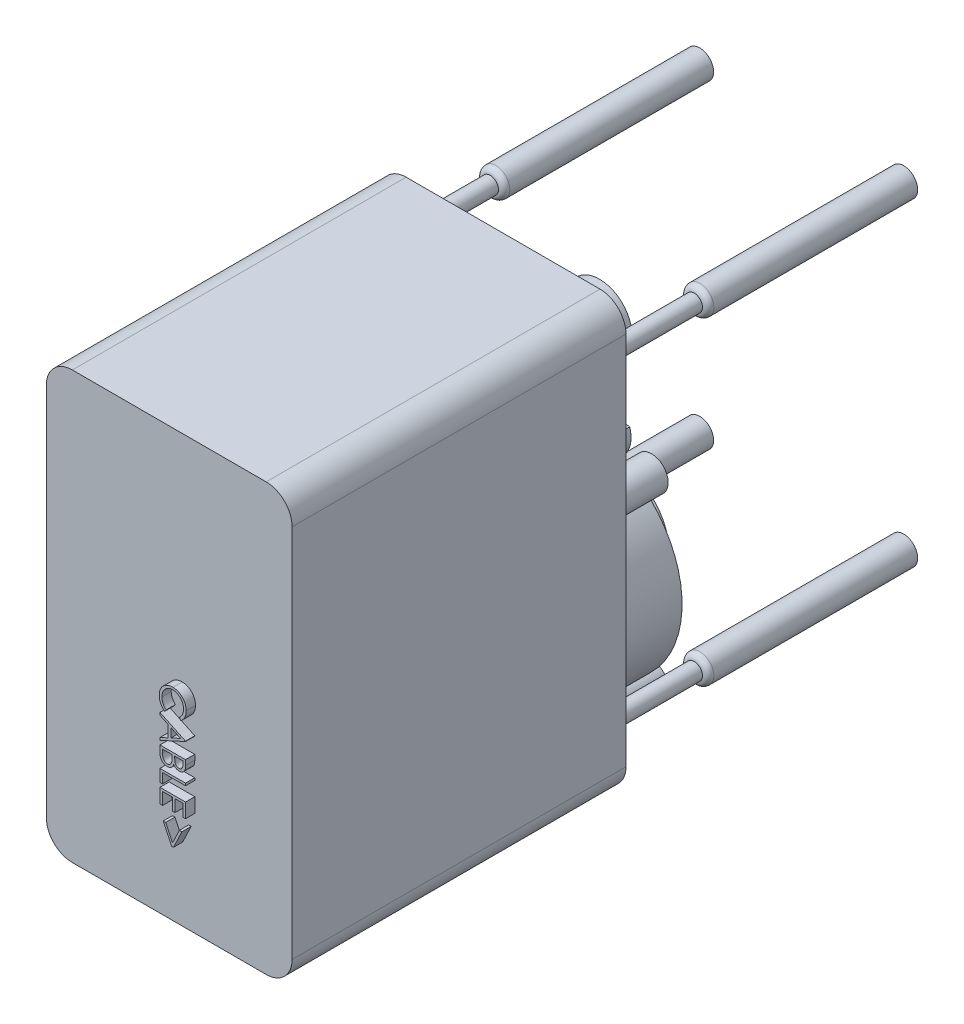
SolidWorks part; units mm, degrees
ref_plane "Front Plane" through (0, 0, 0) normal (0, 0, 1) x (1, 0, 0)
ref_plane "Top Plane" through (0, 0, 0) normal (0, 1, 0) x (1, 0, 0)
ref_plane "Right Plane" through (0, 0, 0) normal (1, 0, 0) x (0, 0, -1)
sketch "Sketch1" plane through (0, 0, 0) normal (0, 0, 1) x (1, 0, 0)
  line L0 (-13.081, 28.829) -> (13.081, 28.829)
  line L1 (-16.637, 25.273) -> (-16.637, -25.273)
  line L2 (-13.081, -28.829) -> (13.081, -28.829)
  line L3 (16.637, 25.273) -> (16.637, -25.273)
  line L4 (-16.637, 28.829) -> (16.637, -28.829) construction
  line L5 (-16.637, -28.829) -> (16.637, 28.829) construction
  line L6 (0, 36.9388) -> (0, -36.9388) construction
  line L7 (-21.0275, 0) -> (21.0275, 0) construction
  arc A0 (16.637, -25.273) -> (13.081, -28.829) centre (13.081, -25.273) cw
  arc A1 (-13.081, -28.829) -> (-16.637, -25.273) centre (-13.081, -25.273) cw
  arc A2 (16.637, 25.273) -> (13.081, 28.829) centre (13.081, 25.273) ccw
  arc A3 (-13.081, 28.829) -> (-16.637, 25.273) centre (-13.081, 25.273) ccw
  circle A4 centre (0, -12.7) radius 7.239
  circle A5 centre (0, 12.7) radius 4.445
  circle A6 centre (0, 14.605) radius 6.35
  circle A7 centre (0, -12.7) radius 14.351
  arc A8 (-3.6204, 1.1868) -> (3.6204, 1.1868) centre (0, 0) ccw
  circle A9 centre (13.97, 21.844) radius 1.016
  circle A10 centre (-13.97, 21.844) radius 1.016
  circle A11 centre (13.97, -21.844) radius 1.016
  circle A12 centre (-13.97, -21.844) radius 1.016
  arc A13 (6.6635, 0.0102) -> (10.0641, -2.4694) centre (8.89, -0.508) cw
  arc A14 (-10.0641, -2.4694) -> (-6.6635, 0.0102) centre (-8.89, -0.508) cw
  arc A15 (-10.0641, -22.9306) -> (-6.6635, -25.4102) centre (-8.89, -24.892) ccw
  arc A16 (6.6635, -25.4102) -> (10.0641, -22.9306) centre (8.89, -24.892) ccw
  point P0 (0, 0)
  dimension "D3" = 3.556
  dimension "D4" = 14.478
  dimension "D5" = 8.89
  dimension "D6" = 12.7
  dimension "D8" = 7.62
  dimension "D10" = 2.032
  dimension "D12" = 28.702
  dimension "D13" = 2.286
  dimension "D1" = 33.274
  dimension "D2" = 57.658
  dimension "D7" = 12.7
  dimension "D9" = 21.844
  dimension "D11" = 13.97
  dimension "D14" = 8.89
  dimension "D15" = 0.508
  dimension "D16" = 0.508
  dimension "D17" = 8.89
  dimension "D18" = 24.892
  dimension "D19" = 24.892
  dimension "D20" = 8.89
  dimension "D21" = 8.89
extrude "Boss-Extrude1" add sketch "Sketch1" against normal blind 10.16 contours A8 A7 A4 | A14 A7 | A7 A8 | A13 A7 | A7 A16 | A7 A15 | A4 region at (0, -12.7, 0) region at (12.8646, -18.0906, 0) region at (9.2197, -0.0559, 0) region at (9.2197, -25.3441, 0) region at (0, -0.8411, 0) region at (-9.2197, -25.3441, 0) region at (-9.2197, -0.0559, 0)
sketch "Sketch2" plane through (0, 0, 0) normal (0, 0, 1) x (1, 0, 0)
  line L0 (-13.081, 28.829) -> (13.081, 28.829)
  line L1 (-16.637, 25.273) -> (-16.637, -25.273)
  line L2 (-13.081, -28.829) -> (13.081, -28.829)
  line L3 (16.637, 25.273) -> (16.637, -25.273)
  line L4 (-16.637, 28.829) -> (16.637, -28.829) construction
  line L5 (-16.637, -28.829) -> (16.637, 28.829) construction
  line L6 (0, 38.9705) -> (0, -34.9071) construction
  line L7 (-9.8575, 0) -> (32.1974, 0) construction
  arc A0 (16.637, -25.273) -> (13.081, -28.829) centre (13.081, -25.273) cw
  arc A1 (-13.081, -28.829) -> (-16.637, -25.273) centre (-13.081, -25.273) cw
  arc A2 (16.637, 25.273) -> (13.081, 28.829) centre (13.081, 25.273) ccw
  arc A3 (-13.081, 28.829) -> (-16.637, 25.273) centre (-13.081, 25.273) ccw
  circle A4 centre (0, -12.7) radius 7.239
  circle A5 centre (0, 12.7) radius 4.445
  circle A6 centre (0, 14.605) radius 6.35
  circle A7 centre (0, -12.7) radius 14.351
  arc A8 (-3.6204, 1.1868) -> (3.6204, 1.1868) centre (0, 0) ccw
  circle A9 centre (13.97, 21.844) radius 1.016
  circle A10 centre (-13.97, 21.844) radius 1.016
  circle A11 centre (13.97, -21.844) radius 1.016
  circle A12 centre (-13.97, -21.844) radius 1.016
  arc A13 (6.6635, 0.0102) -> (10.0641, -2.4694) centre (8.89, -0.508) cw
  arc A14 (-10.0641, -2.4694) -> (-6.6635, 0.0102) centre (-8.89, -0.508) cw
  arc A15 (-10.0641, -22.9306) -> (-6.6635, -25.4102) centre (-8.89, -24.892) ccw
  arc A16 (6.6635, -25.4102) -> (10.0641, -22.9306) centre (8.89, -24.892) ccw
  point P0 (0, 0)
  dimension "D3" = 3.556
  dimension "D4" = 14.478
  dimension "D5" = 8.89
  dimension "D6" = 12.7
  dimension "D8" = 7.62
  dimension "D10" = 2.032
  dimension "D12" = 28.702
  dimension "D13" = 2.286
  dimension "D1" = 33.274
  dimension "D2" = 57.658
  dimension "D7" = 12.7
  dimension "D9" = 21.844
  dimension "D11" = 13.97
  dimension "D14" = 8.89
  dimension "D15" = 0.508
  dimension "D16" = 0.508
  dimension "D17" = 8.89
  dimension "D18" = 24.892
  dimension "D19" = 24.892
  dimension "D20" = 8.89
  dimension "D21" = 8.89
extrude "Boss-Extrude2" add sketch "Sketch2" against normal blind 1.778 separate body contours A5 | A5 A6 region at (0, 12.7, 0) region at (-4.3631, 18.9681, 0)
sketch "Sketch3" plane through (0, 0, -10.16) normal (0, 0, -1) x (-1, 0, 0)
  circle A0 centre (-8.89, -0.508) radius 2.286
  circle A1 centre (8.89, -24.892) radius 2.286
  circle A2 centre (-8.89, -24.892) radius 2.286
  circle A3 centre (8.89, -0.508) radius 2.286
extrude "Boss-Extrude3" add sketch "Sketch3" along normal blind 1.27
sketch "Sketch4" plane through (0, 0, -10.16) normal (0, 0, -1) x (-1, 0, 0)
  line L0 (-13.081, 28.829) -> (13.081, 28.829)
  line L1 (-16.637, 25.273) -> (-16.637, -25.273)
  line L2 (-13.081, -28.829) -> (13.081, -28.829)
  line L3 (16.637, 25.273) -> (16.637, -25.273)
  line L4 (-16.637, 28.829) -> (16.637, -28.829) construction
  line L5 (-16.637, -28.829) -> (16.637, 28.829) construction
  line L6 (0, 23.9866) -> (0, -49.891) construction
  line L7 (7.1619, 0) -> (49.2169, 0) construction
  arc A0 (16.637, -25.273) -> (13.081, -28.829) centre (13.081, -25.273) cw
  arc A1 (-13.081, -28.829) -> (-16.637, -25.273) centre (-13.081, -25.273) cw
  arc A2 (16.637, 25.273) -> (13.081, 28.829) centre (13.081, 25.273) ccw
  arc A3 (-13.081, 28.829) -> (-16.637, 25.273) centre (-13.081, 25.273) ccw
  circle A4 centre (0, -12.7) radius 7.239
  circle A5 centre (0, 12.7) radius 4.445
  circle A6 centre (0, 14.605) radius 6.35
  circle A7 centre (0, -12.7) radius 14.351
  arc A8 (-3.6204, 1.1868) -> (3.6204, 1.1868) centre (0, 0) ccw
  circle A9 centre (13.97, 21.844) radius 1.016
  circle A10 centre (-13.97, 21.844) radius 1.016
  circle A11 centre (13.97, -21.844) radius 1.016
  circle A12 centre (-13.97, -21.844) radius 1.016
  arc A13 (6.6635, 0.0102) -> (10.0641, -2.4694) centre (8.89, -0.508) cw
  arc A14 (-10.0641, -2.4694) -> (-6.6635, 0.0102) centre (-8.89, -0.508) cw
  arc A15 (-10.0641, -22.9306) -> (-6.6635, -25.4102) centre (-8.89, -24.892) ccw
  arc A16 (6.6635, -25.4102) -> (10.0641, -22.9306) centre (8.89, -24.892) ccw
  point P0 (0, 0)
  dimension "D3" = 3.556
  dimension "D4" = 14.478
  dimension "D5" = 8.89
  dimension "D6" = 12.7
  dimension "D8" = 7.62
  dimension "D10" = 2.032
  dimension "D12" = 28.702
  dimension "D13" = 2.286
  dimension "D1" = 33.274
  dimension "D2" = 57.658
  dimension "D7" = 12.7
  dimension "D9" = 21.844
  dimension "D11" = 13.97
  dimension "D14" = 8.89
  dimension "D15" = 0.508
  dimension "D16" = 0.508
  dimension "D17" = 8.89
  dimension "D18" = 24.892
  dimension "D19" = 24.892
  dimension "D20" = 8.89
  dimension "D21" = 8.89
extrude "Boss-Extrude4" add sketch "Sketch4" along normal blind 3.556 contours A7 A8 region at (0, -0.8411, -10.16)
sketch "Sketch5" plane through (0, 0, -1.778) normal (0, 0, -1) x (-1, 0, 0)
  line L0 (-13.081, 28.829) -> (13.081, 28.829)
  line L1 (-16.637, 25.273) -> (-16.637, -25.273)
  line L2 (-13.081, -28.829) -> (13.081, -28.829)
  line L3 (16.637, 25.273) -> (16.637, -25.273)
  line L4 (-16.637, 28.829) -> (16.637, -28.829) construction
  line L5 (-16.637, -28.829) -> (16.637, 28.829) construction
  line L6 (0, 36.0331) -> (0, -37.8445) construction
  line L7 (26.8703, 0) -> (68.9252, 0) construction
  arc A0 (16.637, -25.273) -> (13.081, -28.829) centre (13.081, -25.273) cw
  arc A1 (-13.081, -28.829) -> (-16.637, -25.273) centre (-13.081, -25.273) cw
  arc A2 (16.637, 25.273) -> (13.081, 28.829) centre (13.081, 25.273) ccw
  arc A3 (-13.081, 28.829) -> (-16.637, 25.273) centre (-13.081, 25.273) ccw
  circle A4 centre (0, -12.7) radius 7.239
  circle A5 centre (0, 12.7) radius 4.445
  circle A6 centre (0, 14.605) radius 6.35
  circle A7 centre (0, -12.7) radius 14.351
  arc A8 (-3.6204, 1.1868) -> (3.6204, 1.1868) centre (0, 0) ccw
  circle A9 centre (13.97, 21.844) radius 1.016
  circle A10 centre (-13.97, 21.844) radius 1.016
  circle A11 centre (13.97, -21.844) radius 1.016
  circle A12 centre (-13.97, -21.844) radius 1.016
  arc A13 (6.6635, 0.0102) -> (10.0641, -2.4694) centre (8.89, -0.508) cw
  arc A14 (-10.0641, -2.4694) -> (-6.6635, 0.0102) centre (-8.89, -0.508) cw
  arc A15 (-10.0641, -22.9306) -> (-6.6635, -25.4102) centre (-8.89, -24.892) ccw
  arc A16 (6.6635, -25.4102) -> (10.0641, -22.9306) centre (8.89, -24.892) ccw
  point P0 (0, 0)
  dimension "D3" = 3.556
  dimension "D4" = 14.478
  dimension "D5" = 8.89
  dimension "D6" = 12.7
  dimension "D8" = 7.62
  dimension "D10" = 2.032
  dimension "D12" = 28.702
  dimension "D13" = 2.286
  dimension "D1" = 33.274
  dimension "D2" = 57.658
  dimension "D7" = 12.7
  dimension "D9" = 21.844
  dimension "D11" = 13.97
  dimension "D14" = 8.89
  dimension "D15" = 0.508
  dimension "D16" = 0.508
  dimension "D17" = 8.89
  dimension "D18" = 24.892
  dimension "D19" = 24.892
  dimension "D20" = 8.89
  dimension "D21" = 8.89
extrude "Boss-Extrude5" add sketch "Sketch5" along normal blind 11.43 contours A5 region at (0, 12.7, -1.778)
sketch "Sketch6" plane through (0, 0, 0) normal (0, 0, 1) x (1, 0, 0)
  line L0 (-13.081, 28.829) -> (13.081, 28.829)
  line L1 (-16.637, 25.273) -> (-16.637, -25.273)
  line L2 (-13.081, -28.829) -> (13.081, -28.829)
  line L3 (16.637, 25.273) -> (16.637, -25.273)
  line L4 (-16.637, 28.829) -> (16.637, -28.829) construction
  line L5 (-16.637, -28.829) -> (16.637, 28.829) construction
  line L6 (0, 36.0885) -> (0, -37.789) construction
  line L7 (-47.9194, 0) -> (-5.8644, 0) construction
  arc A0 (16.637, -25.273) -> (13.081, -28.829) centre (13.081, -25.273) cw
  arc A1 (-13.081, -28.829) -> (-16.637, -25.273) centre (-13.081, -25.273) cw
  arc A2 (16.637, 25.273) -> (13.081, 28.829) centre (13.081, 25.273) ccw
  arc A3 (-13.081, 28.829) -> (-16.637, 25.273) centre (-13.081, 25.273) ccw
  circle A4 centre (0, -12.7) radius 7.239
  circle A5 centre (0, 12.7) radius 4.445
  circle A6 centre (0, 14.605) radius 6.35
  circle A7 centre (0, -12.7) radius 14.351
  arc A8 (-3.6204, 1.1868) -> (3.6204, 1.1868) centre (0, 0) ccw
  circle A9 centre (13.97, 21.844) radius 1.143
  circle A10 centre (-13.97, 21.844) radius 1.143
  circle A11 centre (13.97, -21.844) radius 1.143
  circle A12 centre (-13.97, -21.844) radius 1.143
  arc A13 (6.6635, 0.0102) -> (10.0641, -2.4694) centre (8.89, -0.508) cw
  arc A14 (-10.0641, -2.4694) -> (-6.6635, 0.0102) centre (-8.89, -0.508) cw
  arc A15 (-10.0641, -22.9306) -> (-6.6635, -25.4102) centre (-8.89, -24.892) ccw
  arc A16 (6.6635, -25.4102) -> (10.0641, -22.9306) centre (8.89, -24.892) ccw
  point P0 (0, 0)
  dimension "D3" = 3.556
  dimension "D4" = 14.478
  dimension "D5" = 8.89
  dimension "D6" = 12.7
  dimension "D8" = 7.62
  dimension "D10" = 2.286
  dimension "D12" = 28.702
  dimension "D13" = 2.286
  dimension "D1" = 33.274
  dimension "D2" = 57.658
  dimension "D7" = 12.7
  dimension "D9" = 21.844
  dimension "D11" = 13.97
  dimension "D14" = 8.89
  dimension "D15" = 0.508
  dimension "D16" = 0.508
  dimension "D17" = 8.89
  dimension "D18" = 24.892
  dimension "D19" = 24.892
  dimension "D20" = 8.89
  dimension "D21" = 8.89
extrude "Boss-Extrude6" add sketch "Sketch6" against normal blind 15.494 separate body contours A10 | A9 | A12 | A11 region at (13.97, 21.844, 0) region at (-13.97, 21.844, 0) region at (13.97, -21.844, 0) region at (-13.97, -21.844, 0)
sketch "Sketch7" plane through (0, 0, -10.16) normal (0, 0, -1) x (-1, 0, 0)
  line L0 (-13.081, 28.829) -> (13.081, 28.829)
  line L1 (-16.637, 25.273) -> (-16.637, -25.273)
  line L2 (-13.081, -28.829) -> (13.081, -28.829)
  line L3 (16.637, 25.273) -> (16.637, -25.273)
  line L4 (-16.637, 28.829) -> (16.637, -28.829) construction
  line L5 (-16.637, -28.829) -> (16.637, 28.829) construction
  line L6 (0, 26.9541) -> (0, -46.9235) construction
  line L7 (8.0915, 0) -> (50.1464, 0) construction
  arc A0 (16.637, -25.273) -> (13.081, -28.829) centre (13.081, -25.273) cw
  arc A1 (-13.081, -28.829) -> (-16.637, -25.273) centre (-13.081, -25.273) cw
  arc A2 (16.637, 25.273) -> (13.081, 28.829) centre (13.081, 25.273) ccw
  arc A3 (-13.081, 28.829) -> (-16.637, 25.273) centre (-13.081, 25.273) ccw
  circle A4 centre (0, -12.7) radius 7.239
  circle A5 centre (0, 12.7) radius 4.445
  circle A6 centre (0, 14.605) radius 6.35
  circle A7 centre (0, -12.7) radius 14.351
  arc A8 (-3.6204, 1.1868) -> (3.6204, 1.1868) centre (0, 0) ccw
  circle A9 centre (13.97, 21.844) radius 1.016
  circle A10 centre (-13.97, 21.844) radius 1.016
  circle A11 centre (13.97, -21.844) radius 1.016
  circle A12 centre (-13.97, -21.844) radius 1.016
  arc A13 (6.6635, 0.0102) -> (10.0641, -2.4694) centre (8.89, -0.508) cw
  arc A14 (-10.0641, -2.4694) -> (-6.6635, 0.0102) centre (-8.89, -0.508) cw
  arc A15 (-10.0641, -22.9306) -> (-6.6635, -25.4102) centre (-8.89, -24.892) ccw
  arc A16 (6.6635, -25.4102) -> (10.0641, -22.9306) centre (8.89, -24.892) ccw
  point P0 (0, 0)
  dimension "D3" = 3.556
  dimension "D4" = 14.478
  dimension "D5" = 8.89
  dimension "D6" = 12.7
  dimension "D8" = 7.62
  dimension "D10" = 2.032
  dimension "D12" = 28.702
  dimension "D13" = 2.286
  dimension "D1" = 33.274
  dimension "D2" = 57.658
  dimension "D7" = 12.7
  dimension "D9" = 21.844
  dimension "D11" = 13.97
  dimension "D14" = 8.89
  dimension "D15" = 0.508
  dimension "D16" = 0.508
  dimension "D17" = 8.89
  dimension "D18" = 24.892
  dimension "D19" = 24.892
  dimension "D20" = 8.89
  dimension "D21" = 8.89
extrude "Boss-Extrude7" add sketch "Sketch7" along normal blind 5.334 contours A4 region at (0, -12.7, -10.16)
sketch "Sketch8" plane through (0, 0, 0) normal (0, 0, 1) x (1, 0, 0)
  line L1 (-13.2715, 29.21) -> (13.2715, 29.21)
  line L2 (-16.8275, 25.654) -> (-16.8275, -25.654)
  line L3 (-13.2715, -29.21) -> (13.2715, -29.21)
  line L4 (16.8275, 25.654) -> (16.8275, -25.654)
  line L5 (-16.8275, 29.21) -> (16.8275, -29.21) construction
  line L6 (-16.8275, -29.21) -> (16.8275, 29.21) construction
  arc A8 (16.8275, -25.654) -> (13.2715, -29.21) centre (13.2715, -25.654) cw
  arc A13 (-13.2715, -29.21) -> (-16.8275, -25.654) centre (-13.2715, -25.654) cw
  arc A14 (16.8275, 25.654) -> (13.2715, 29.21) centre (13.2715, 25.654) ccw
  arc A15 (-13.2715, 29.21) -> (-16.8275, 25.654) centre (-13.2715, 25.654) ccw
  point P0 (0, 0)
  dimension "D3" = 3.556
  dimension "D1" = 33.655
  dimension "D23" = 58.42
extrude "Boss-Extrude8" add sketch "Sketch8" along normal blind 45.72
sketch "Sketch9" plane through (0, 0, -15.494) normal (0, 0, -1) x (-1, 0, 0)
  circle A0 centre (-13.97, 21.844) radius 1.905
  circle A1 centre (13.97, 21.844) radius 1.905
  circle A2 centre (13.97, -21.844) radius 1.905
  circle A3 centre (-13.97, -21.844) radius 1.905
  dimension "D1" = 3.81
extrude "Boss-Extrude9" add sketch "Sketch9" against normal blind 3.302 and the other way blind 25.4
sketch "Sketch10" plane through (0, 0, 45.72) normal (0, 0, 1) x (1, 0, 0)
  line L0 (0, 0) -> (0, -29.21) construction
  line L1 (-13.2715, -29.21) -> (13.2715, -29.21) construction
  text T0 "CABLE >"
extrude "Boss-Extrude10" add sketch "Sketch10" along normal blind 1.27
fillet "Fillet1" radius 0.7937 4 edges at (-15.875, -21.844, -12.192) (12.065, -21.844, -12.192) (12.065, 21.844, -12.192) (-15.875, 21.844, -12.192)
